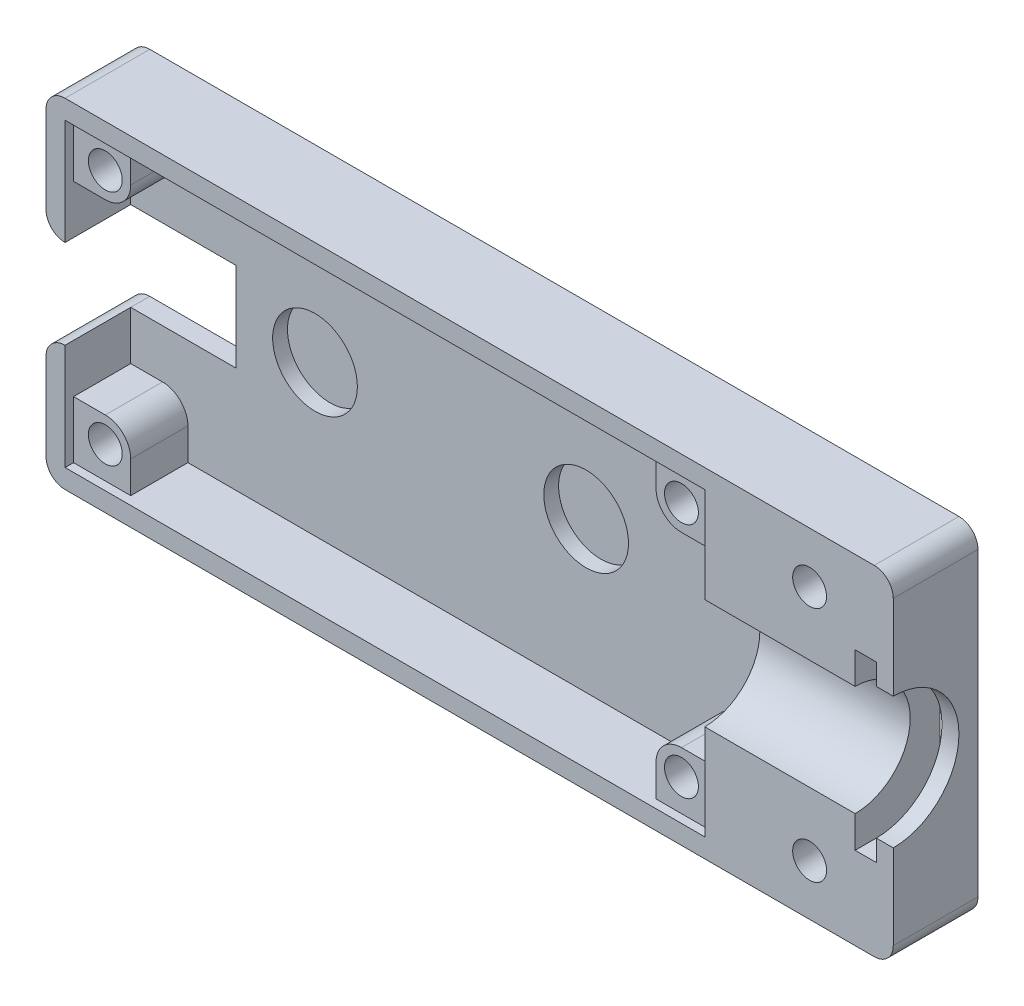
SolidWorks part; units mm, degrees
ref_plane "Front Plane" through (0, 0, 0) normal (0, 0, 1) x (1, 0, 0)
ref_plane "Top Plane" through (0, 0, 0) normal (0, 1, 0) x (1, 0, 0)
ref_plane "Right Plane" through (0, 0, 0) normal (1, 0, 0) x (0, 0, -1)
sketch "Sketch4" plane through (0, 0, 0) normal (0, 0, 1) x (1, 0, 0)
  line L0 (0, 40) -> (0, 25.25)
  line L1 (0, 0) -> (100, 0)
  line L2 (0, 14.75) -> (0, 0)
  line L3 (0, 40) -> (100, 40)
  line L4 (100, 0) -> (100, 40)
  line L5 (14.7, 14.75) -> (14.7, 25.25)
  line L6 (14.7, 25.25) -> (0, 25.25)
  line L7 (14.7, 14.75) -> (0, 14.75)
  line L8 (14.7, 20) -> (100, 20) construction
  line L9 (0, 0) -> (0, 40) construction
  dimension "D1" = 40
  dimension "D2" = 14.7
  dimension "D4" = 10.5
  dimension "D5" = 100
extrude "body" add sketch "Sketch4" along normal blind 10
sketch "Sketch10" plane through (0, 0, 10) normal (0, 0, 1) x (1, 0, 0)
  line L0 (0, 40) -> (0, 0) construction
  line L1 (0, 20) -> (100, 20) construction
  line L2 (100, 0) -> (100, 40) construction
  line L4 (77.75, 2.25) -> (2.25, 2.25)
  line L5 (77.75, 2.25) -> (77.75, 37.75)
  line L6 (77.75, 37.75) -> (2.25, 37.75)
  line L7 (2.25, 2.25) -> (2.25, 37.75)
  line L8 (77.75, 2.25) -> (2.25, 37.75) construction
  line L9 (77.75, 37.75) -> (2.25, 2.25) construction
  point P8 (40, 20)
  dimension "D1" = 75.5
  dimension "D2" = 35.5
  dimension "D3" = 2.25
extrude "pcb-recess" cut sketch "Sketch10" against normal offset from surface (7.75 mm away) 2.25 up to face at (28.675, 20, 0)
sketch "Sketch11" plane through (0, 0, 2.25) normal (0, 0, 1) x (1, 0, 0)
  line L0 (2.25, 37.75) -> (2.25, 2.25) construction
  line L1 (2.25, 20) -> (77.75, 20) construction
  line L2 (77.75, 2.25) -> (77.75, 37.75) construction
  line L3 (6, 37.75) -> (6, 2.25) construction
  line L4 (77.75, 37.75) -> (2.25, 37.75) construction
  line L5 (2.25, 2.25) -> (77.75, 2.25) construction
  line L6 (74, 37.75) -> (74, 2.25) construction
  line L7 (77.75, 37.75) -> (2.25, 37.75) construction
  line L8 (2.25, 2.25) -> (77.75, 2.25) construction
  line L9 (2.25, 34) -> (77.75, 34) construction
  line L10 (2.25, 6) -> (77.75, 6) construction
  line L11 (9, 34) -> (9, 37.75)
  line L12 (6, 31) -> (2.25, 31)
  line L13 (2.25, 31) -> (2.25, 37.75)
  line L14 (2.25, 37.75) -> (9, 37.75)
  line L15 (71, 34) -> (71, 37.75)
  line L16 (71, 37.75) -> (77.75, 37.75)
  line L17 (77.75, 37.75) -> (77.75, 31)
  line L18 (77.75, 37.75) -> (77.75, 2.25) construction
  line L19 (77.75, 31) -> (74, 31)
  line L20 (74, 9) -> (77.75, 9)
  line L21 (77.75, 9) -> (77.75, 2.25)
  line L22 (77.75, 2.25) -> (71, 2.25)
  line L23 (71, 2.25) -> (71, 6)
  line L24 (2.25, 9) -> (6, 9)
  line L25 (9, 2.25) -> (9, 6)
  line L26 (77.75, 2.25) -> (2.25, 2.25) construction
  circle A0 centre (6, 34) radius 3
  circle A1 centre (74, 34) radius 3
  circle A2 centre (74, 6) radius 3
  circle A3 centre (6, 6) radius 3
  point P20 (40, 20)
  line M9 (2.25, 14.75) -> (2.25, 2.25)
  line M10 (2.25, 2.25) -> (77.75, 2.25)
  line M11 (77.75, 2.25) -> (77.75, 37.75)
  line M12 (77.75, 37.75) -> (2.25, 37.75)
  line M13 (2.25, 37.75) -> (2.25, 25.25)
  dimension "D5" = 6
  dimension "D6" = 6
  dimension "D7" = 6
  dimension "D8" = 6
  dimension "D1" = 34
  dimension "D2" = 34
  dimension "D3" = 14
  dimension "D4" = 14
extrude "pcb-boss" add sketch "Sketch11" along normal offset from surface (6.75 mm away) 1 contours A0 | A0 L11 L12 M12 M13 | A1 L19 L15 M11 M12 | A1 | A2 | A2 L23 L20 M10 M11 | A3 | A3 L24 L25 M9 M10 region at (3.8112, 36.1888, 2.25) region at (6, 34, 2.25) region at (5.625, 2.3455, 2.25) region at (77.6545, 5.625, 2.25) region at (74.375, 37.6545, 2.25) region at (74, 34, 2.25) region at (74, 6, 2.25) region at (6, 6, 2.25) up to face at (30.375, 20, 10)
fillet "Fillet2" radius 2.25 2 edges at (0, 14.75, 5) (0, 25.25, 5)
sketch "Sketch12" plane through (0, 0, 9) normal (0, 0, 1) x (1, 0, 0)
  circle A0 centre (6, 34) radius 2
  circle A1 centre (74, 34) radius 2
  circle A2 centre (74, 6) radius 2
  circle A3 centre (6, 6) radius 2
  dimension "D1" = 4
  dimension "D2" = 4
  dimension "D3" = 4
  dimension "D4" = 4
extrude "m3-inserts" cut sketch "Sketch12" against normal blind 5.5
fillet "Fillet3" radius 2.25 4 edges at (0, 0, 5) (0, 40, 5) (100, 0, 5) (100, 40, 5)
sketch "Sketch27" plane through (0, 0, 2.25) normal (0, 0, 1) x (1, 0, 0)
  line L0 (2.25, 20) -> (77.75, 20) construction
  line L1 (77.75, 31) -> (77.75, 9) construction
  line L2 (2.25, 25.25) -> (2.25, 14.75) construction
  circle A0 centre (24, 20) radius 5
  circle A1 centre (56, 20) radius 5
  point P2 (2.25, 20)
  point P5 (40, 20)
  dimension "D1" = 10
  dimension "D2" = 10
  dimension "D3" = 16
  dimension "D4" = 16
extrude "magnets" cut sketch "Sketch27" against normal offset from surface (1.75 mm away) 0.5 up to face at (30.9263, 20, 0)
sketch "Sketch29" plane through (0, 0, 10) normal (0, 0, 1) x (1, 0, 0)
  line L1 (100, 12.25) -> (100, 27.75)
  line L2 (100, 2.25) -> (100, 37.75) construction
  line L5 (100, 27.75) -> (98, 27.75)
  line L6 (98, 27.75) -> (98, 12.25)
  line L7 (100, 20) -> (98, 20) construction
  line L8 (100, 12.25) -> (98, 12.25)
  dimension "D1" = 2
  dimension "D2" = 15.5
revolve "hirose-front" cut sketch "Sketch29" angle 360 about L7 region at (99, 23.875, 10)
sketch "Sketch30" plane through (0, 0, 10) normal (0, 0, 1) x (1, 0, 0)
  line L0 (98, 12.25) -> (98, 27.75) construction
  line L1 (95.5, 30.25) -> (98, 30.25)
  line L2 (95.5, 30.25) -> (95.5, 9.75)
  line L3 (95.5, 9.75) -> (98, 9.75)
  line L4 (98, 30.25) -> (98, 9.75)
  point P4 (98, 20)
  point P5 (93, 20)
  dimension "D1" = 20.5
  dimension "D2" = 2.5
extrude "hirose-mid" cut sketch "Sketch30" against normal through all
sketch "Sketch31" plane through (0, 0, 10) normal (0, 0, 1) x (1, 0, 0)
  line L0 (90.125, 20) -> (90.125, 34) construction
  line L1 (80.25, 40) -> (80.25, 0) construction
  line L3 (97.75, 40) -> (2.25, 40) construction
  line L5 (100, 27.75) -> (100, 12.25) construction
  line L7 (2.25, 0) -> (97.75, 0) construction
  line L8 (77.75, 2.25) -> (77.75, 37.75) construction
  line L9 (80.25, 20) -> (100, 20) construction
  circle A0 centre (90.125, 34) radius 2
  circle A1 centre (90.125, 6) radius 2
  point P17 (90.25, 20)
  dimension "D1" = 4
  dimension "D2" = 2.5
  dimension "D3" = 14
extrude "Cut-Extrude14" cut sketch "Sketch31" against normal blind 5.5
sketch "Sketch32" plane through (0, 0, 10) normal (0, 0, 1) x (1, 0, 0)
  line L0 (95.5, 30.25) -> (95.5, 9.75) construction
  line L1 (95.5, 26.5) -> (77.75, 26.5)
  line L2 (95.5, 26.5) -> (95.5, 13.5)
  line L3 (95.5, 13.5) -> (77.75, 13.5)
  line L4 (77.75, 26.5) -> (77.75, 13.5)
  line L5 (77.75, 20) -> (95.5, 20) construction
  line L6 (77.75, 31) -> (77.75, 9) construction
  point P8 (95.5, 20)
  point P9 (77.75, 20)
  dimension "D1" = 13
revolve "hirose-back" cut sketch "Sketch32" angle 360 about L5 region at (86.625, 23.25, 10)
